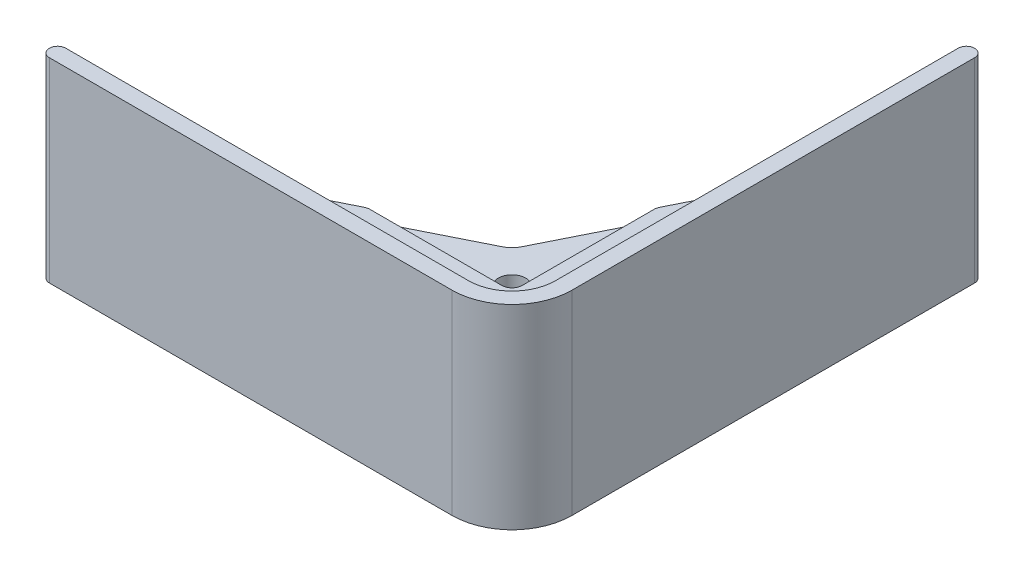
SolidWorks part; units mm, degrees
material "Nylon 101"
ref_plane "Front Plane" through (0, 0, 0) normal (0, 0, 1) x (1, 0, 0)
ref_plane "Top Plane" through (0, 0, 0) normal (0, 1, 0) x (1, 0, 0)
ref_plane "Right Plane" through (0, 0, 0) normal (1, 0, 0) x (0, 0, -1)
sketch "Sketch1" plane through (0, 0, 0) normal (0, 1, 0) x (1, 0, 0)
  line L0 (0, -18.542) -> (-127, -18.542)
  line L1 (18.542, 0) -> (18.542, 127)
  line L2 (-127, -18.542) -> (-127, -13.462)
  line L3 (-127, -13.462) -> (0, -13.462)
  line L4 (13.462, 0) -> (13.462, 127)
  line L5 (13.462, 127) -> (18.542, 127)
  line L6 (-6.0067, 12.0476) -> (-57.1711, -13.462)
  line L7 (-12.0476, 6.0067) -> (13.462, 57.1711)
  circle A0 centre (0, 0) radius 4.2862
  arc A1 (0, -18.542) -> (18.542, 0) centre (0, 0) ccw
  circle A2 centre (0, 0) radius 13.462
  dimension "D1" = 8.5725
  dimension "D4" = 5.08
  dimension "D5" = 127
  dimension "D6" = 26.5
  dimension "D3" = 13.462
extrude "Boss-Extrude1" add sketch "Sketch1" along normal blind 50.8 contours A2 L3 L2 L0 A1 L1 L5 L4 | A2 A0 | A2 L3 | A2 L4 L7 | A2 L6 L7 region at (-63.5, 0, 16.4837) region at (-26.4429, 0, 6.2746) region at (-11.1237, 0, 6.8835) region at (6.2746, 0, -26.4429) region at (-9.6262, 0, -9.6262)
fillet "Fillet2" radius 2.54 4 edges at (13.462, 25.4, -127) (18.542, 25.4, -127) (-127, 25.4, 13.462) (-127, 25.4, 18.542)
ref_plane "Plane1" through (0, 25.4, 0) normal (0, 1, 0) x (1, 0, 0)
sketch "Sketch7" plane through (0, 50.8, 0) normal (0, 1, 0) x (1, 0, 0)
  line L1 (4.826, -4.826) -> (-39.8499, -4.826)
  line L2 (4.826, -4.826) -> (4.826, 39.8499)
  line L3 (4.826, 39.8499) -> (-39.8499, 39.8499)
  line L4 (-39.8499, -4.826) -> (-39.8499, 39.8499)
  line L6 (-10.0378, 10.0378) -> (-57.1711, -13.462) construction
  circle A1 centre (0, 0) radius 4.2862 construction
  dimension "D1" = 4.826
  dimension "D2" = 4.826
extrude "Cut-Extrude3" cut sketch "Sketch7" against normal blind 3.429
fillet "Fillet9" radius 3.175 3 edges at (4.826, 49.0855, -39.8499) (4.826, 49.0855, 4.826) (-39.8499, 49.0855, 4.826)
sketch "Sketch8" plane through (0, 25.4, 0) normal (0, 1, 0) x (1, 0, 0)
  line L0 (0, -13.462) -> (-124.46, -13.462)
  line L10 (13.462, 57.1711) -> (5.1596, 40.519)
  line L11 (4.826, 39.1023) -> (4.826, -1.651)
  line L12 (1.651, -4.826) -> (-39.1023, -4.826)
  line L13 (-40.519, -5.1596) -> (-57.1711, -13.462)
  line L14 (-57.1711, -13.462) -> (-124.46, -13.462)
  line L16 (-124.46, -18.542) -> (0, -18.542)
  line L17 (18.542, 0) -> (18.542, 124.46)
  line L19 (13.462, 124.46) -> (13.462, 57.1711)
  line L26 (-124.46, -18.542) -> (0, -18.542)
  line L27 (18.542, 0) -> (18.542, 124.46)
  line L29 (13.462, 124.46) -> (13.462, 0)
  arc A0 (0, -13.462) -> (13.462, 0) centre (0, 0) ccw
  arc A9 (5.1596, 40.519) -> (4.826, 39.1023) centre (8.001, 39.1023) ccw
  arc A10 (1.651, -4.826) -> (4.826, -1.651) centre (1.651, -1.651) ccw
  arc A11 (-39.1023, -4.826) -> (-40.519, -5.1596) centre (-39.1023, -8.001) ccw
  arc A12 (-124.46, -13.462) -> (-127, -16.002) centre (-124.46, -16.002) ccw
  arc A13 (-127, -16.002) -> (-124.46, -18.542) centre (-124.46, -16.002) ccw
  arc A14 (0, -18.542) -> (18.542, 0) centre (0, 0) ccw
  arc A15 (18.542, 124.46) -> (16.002, 127) centre (16.002, 124.46) ccw
  arc A16 (16.002, 127) -> (13.462, 124.46) centre (16.002, 124.46) ccw
  arc A21 (-124.46, -13.462) -> (-127, -16.002) centre (-124.46, -16.002) ccw
  arc A22 (-127, -16.002) -> (-124.46, -18.542) centre (-124.46, -16.002) ccw
  arc A23 (0, -18.542) -> (18.542, 0) centre (0, 0) ccw
  arc A24 (18.542, 124.46) -> (16.002, 127) centre (16.002, 124.46) ccw
  arc A25 (16.002, 127) -> (13.462, 124.46) centre (16.002, 124.46) ccw
  dimension "D1" = 0
extrude "Boss-Extrude2" add sketch "Sketch8" along normal mid plane 60.325
fillet "Fillet10" radius 6.35 3 edges at (-10.0378, 23.6855, -10.0378) (-57.1711, 25.4, 13.462) (13.462, 25.4, -57.1711)
equation "\"D1@Sketch1\"=.3125+0.025"
